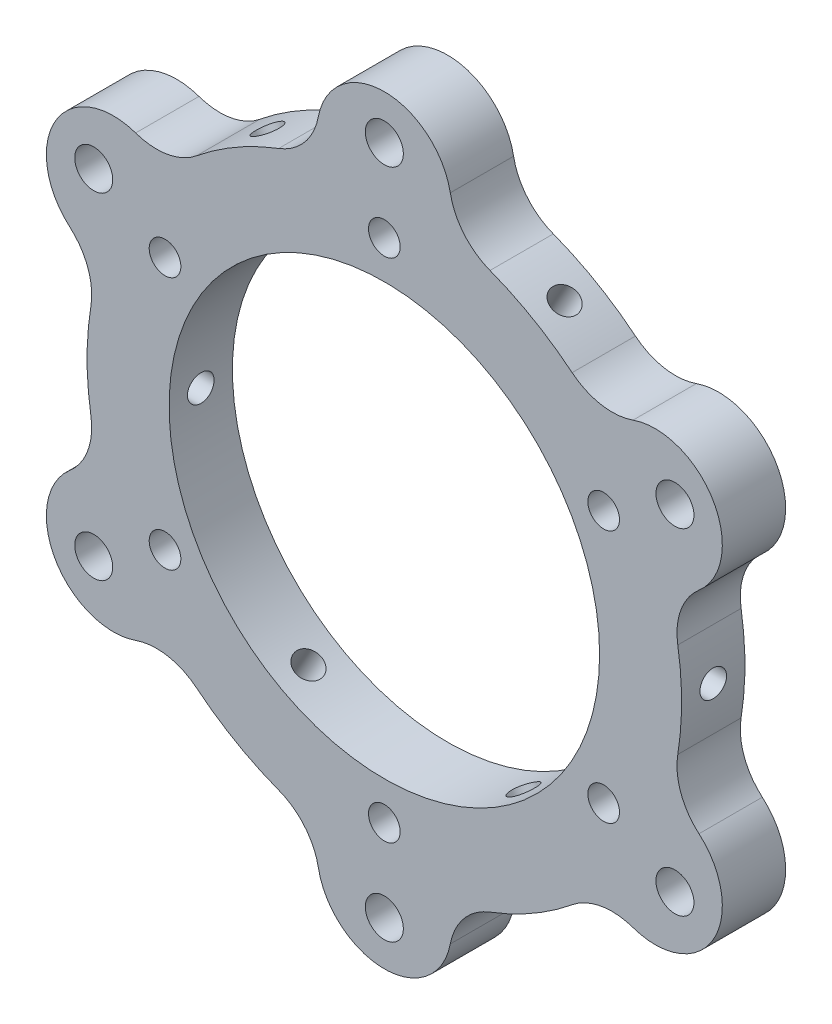
SolidWorks part; units mm, degrees
material "6063-T6"
ref_plane "Front Plane" through (0, 0, 0) normal (0, 0, 1) x (1, 0, 0)
ref_plane "Top Plane" through (0, 0, 0) normal (0, 1, 0) x (1, 0, 0)
ref_plane "Right Plane" through (0, 0, 0) normal (1, 0, 0) x (0, 0, -1)
sketch "Sketch5" plane through (0, 0, 0) normal (0, 1, 0) x (1, 0, 0)
  line L0 (0, -16.5008) -> (0, 15.0181) construction
ref_plane "Plane1" through (0, 0, 0) normal (-0.5, 0.866, 0) x (0, 0, -1)
sketch "Sketch2" plane through (0, 0, 0) normal (0, 0, 1) x (1, 0, 0)
  line L0 (0, 0) -> (0, 53) construction
  line L1 (0, 0) -> (0, 40) construction
  line L2 (0, 0) -> (0, 53) construction
  circle A0 centre (0, 0) radius 34
  circle A1 centre (0, 0) radius 60
  circle A2 centre (0, 53) radius 3
  circle A3 centre (45.8993, 26.5) radius 3
  circle A4 centre (45.8993, -26.5) radius 3
  circle A5 centre (0, -53) radius 3
  circle A6 centre (-45.8993, -26.5) radius 3
  circle A7 centre (-45.8993, 26.5) radius 3
  circle A11 centre (0, 0) radius 53 construction
  circle A12 centre (0, 40) radius 2.5
  circle A13 centre (34.641, 20) radius 2.5
  circle A14 centre (34.641, -20) radius 2.5
  circle A15 centre (0, -40) radius 2.5
  circle A16 centre (-34.641, -20) radius 2.5
  circle A17 centre (-34.641, 20) radius 2.5
  circle A18 centre (0, 0) radius 44.45 construction
  arc A19 (-16.6885, 43.8839) -> (16.6885, 43.8839) centre (0, 0) ccw
  arc A21 (-10.4177, 51.3701) -> (10.4177, 51.3701) centre (0, 49.3971) cw
  arc A22 (10.4177, 51.3701) -> (16.6885, 43.8839) centre (20.2431, 53.2308) ccw
  circle A23 centre (0, 0) radius 46.95 construction
  arc A24 (-10.4177, 51.3701) -> (-16.6885, 43.8839) centre (-20.2431, 53.2308) cw
  arc A25 (39.2789, 34.707) -> (49.6966, 16.663) centre (42.7791, 24.6985) cw
  arc A26 (39.2789, 34.707) -> (29.6603, 36.3946) centre (35.9777, 44.1464) cw
  arc A27 (49.6966, 16.663) -> (46.3488, 7.4892) centre (56.2208, 9.0844) ccw
  arc A28 (49.6966, -16.663) -> (39.2789, -34.707) centre (42.7791, -24.6985) cw
  arc A29 (49.6966, -16.663) -> (46.3488, -7.4892) centre (56.2208, -9.0844) cw
  arc A30 (39.2789, -34.707) -> (29.6603, -36.3946) centre (35.9777, -44.1464) ccw
  arc A31 (10.4177, -51.3701) -> (-10.4177, -51.3701) centre (0, -49.3971) cw
  arc A32 (10.4177, -51.3701) -> (16.6885, -43.8839) centre (20.2431, -53.2308) cw
  arc A33 (-10.4177, -51.3701) -> (-16.6885, -43.8839) centre (-20.2431, -53.2308) ccw
  arc A34 (-39.2789, -34.707) -> (-49.6966, -16.663) centre (-42.7791, -24.6985) cw
  arc A35 (-39.2789, -34.707) -> (-29.6603, -36.3946) centre (-35.9777, -44.1464) cw
  arc A36 (-49.6966, -16.663) -> (-46.3488, -7.4892) centre (-56.2208, -9.0844) ccw
  arc A37 (-49.6966, 16.663) -> (-39.2789, 34.707) centre (-42.7791, 24.6985) cw
  arc A38 (-49.6966, 16.663) -> (-46.3488, 7.4892) centre (-56.2208, 9.0844) cw
  arc A39 (-39.2789, 34.707) -> (-29.6603, 36.3946) centre (-35.9777, 44.1464) ccw
  point P24 (0, 0)
  point P42 (46.95, 0)
  point P43 (0, 0)
  point P46 (10, 45.8727)
  point P49 (-10, 45.8727)
  point P84 (0, 0)
  dimension "D1" = 6
  dimension "D2" = 68
  dimension "D3" = 120
  dimension "D6" = 6
  dimension "D7" = 88.9
  dimension "D9" = 5
  dimension "D4" = 0
  dimension "D11" = 20
  dimension "D12" = 10
  dimension "D5" = 6
  dimension "D8" = 2.5
  dimension "D10" = 40
  dimension "D13" = 6
extrude "Boss-Extrude1" add sketch "Sketch2" along normal blind 10 contours A21 A24 A19 A22 A0 A2 A12 A13 A14 A15 A16 A17 | A39 A37 A38 A19 A7 | A27 A25 A26 A19 A3 | A33 A31 A32 A19 A5 | A36 A34 A35 A19 A6 | A30 A28 A29 A19 A4 region at (52.8637, 22.986, 0) region at (46.3383, -34.2883, 0) region at (5.856, 56.4663, 0) region at (-6.5275, -57.2769, 0) region at (-46.3383, 34.2883, 0) region at (-52.8637, -22.986, 0)
sketch "Sketch4" plane through (0, 0, 0) normal (-0.5, 0.866, 0) x (0, 0, -1)
  line L0 (0, 0) -> (-10, 0) construction
  line L3 (-16.5008, 0) -> (15.0181, 0) construction
  line L7 (0, -7.4892) -> (0, 7.4892)
  line L8 (0, 7.4892) -> (-10, 7.4892)
  line L9 (-10, 7.4892) -> (-10, -7.4892)
  line L10 (-10, -7.4892) -> (0, -7.4892)
  line L11 (0, -7.4892) -> (0, 7.4892)
  line L12 (0, 7.4892) -> (-10, 7.4892)
  line L13 (-10, 7.4892) -> (-10, -7.4892)
  line L14 (-10, -7.4892) -> (0, -7.4892)
  circle A4 centre (-5, 0) radius 2.1
  point P2 (0, 0)
  point P5 (-0.3087, -0.2201)
  point P7 (-3.9118, 0)
  point P14 (0, 0)
  dimension "D1" = 0
  dimension "D2" = 4.2
extrude "Cut-Extrude1" cut sketch "Sketch4" against normal through all both and the other way through all contours L0 A4 | A4 L0 region at (0.7719, 0.4456, 5) region at (-0.7719, -0.4456, 5)
pattern_circular "CirPattern1" count 6 over 360 about axis through (0, 0, 16.5008) along (0, 0, -1) of "Cut-Extrude1" reverse direction yes
